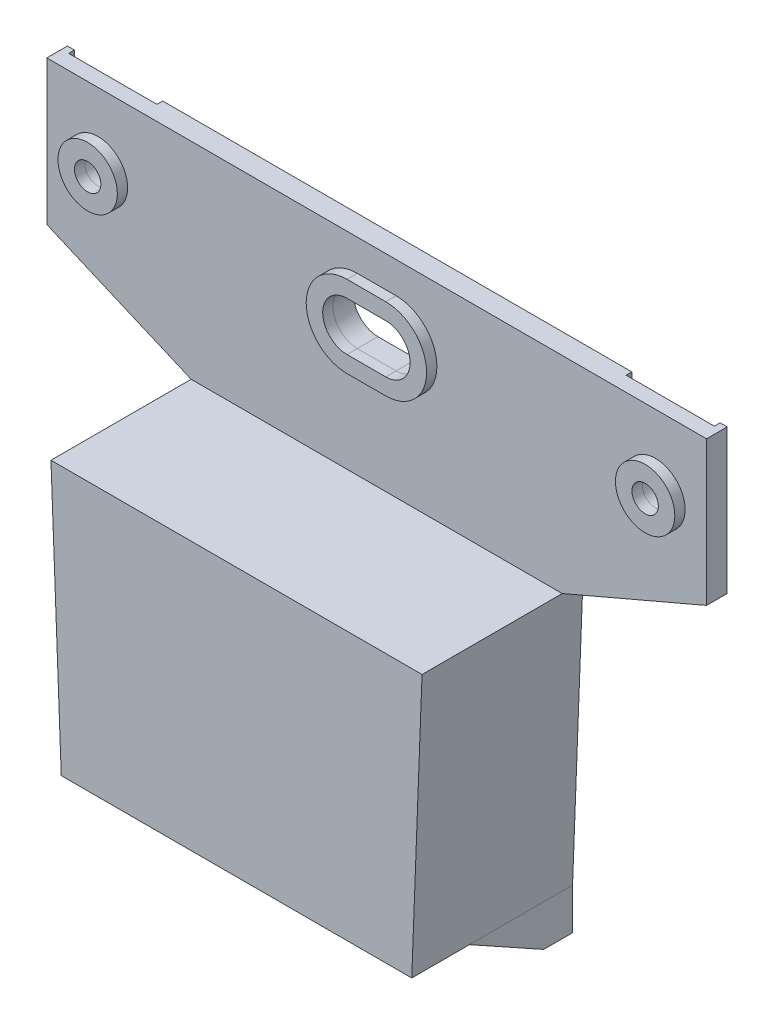
SolidWorks part; units mm, degrees
note: The reader was unsure of these and kept them because the rebuilt part matched: shared geometry of "Sketch17<2>".
ref_plane "Front Plane" through (0, 0, 0) normal (0, 0, 1) x (1, 0, 0)
ref_plane "Top Plane" through (0, 0, 0) normal (0, 1, 0) x (1, 0, 0)
ref_plane "Right Plane" through (0, 0, 0) normal (1, 0, 0) x (0, 0, -1)
sketch "Sketch1" plane through (0, 0, 0) normal (0, 0, 1) x (1, 0, 0)
  line L0 (-53.975, 0) -> (53.975, 0)
  line L1 (53.975, 0) -> (57.15, 82.55)
  line L2 (57.15, 82.55) -> (101.6, 101.6)
  line L3 (101.6, 101.6) -> (101.6, 146.05)
  line L4 (101.6, 146.05) -> (-101.6, 146.05)
  line L5 (-101.6, 146.05) -> (-101.6, 101.6)
  line L6 (-101.6, 101.6) -> (-57.15, 82.55)
  line L7 (-57.15, 82.55) -> (-53.975, 0)
  point P4 (0, 0)
  point P7 (0, 0)
  point P16 (0, 146.05)
  dimension "D1" = 44.45
  dimension "D2" = 44.45
  dimension "D3" = 146.05
  dimension "D4" = 107.95
  dimension "D5" = 203.2
  dimension "D6" = 114.3
  dimension "D7" = 19.05
base flange "Main Body" sketch "Sketch1" thickness 6.35 reverse thickness direction no parameters "D1"=1
sketch "Sketch6" plane through (0, 0, 0) normal (0, 0, 1) x (1, 0, 0)
  line L0 (53.975, 0) -> (-53.975, 0)
  line L1 (-53.975, 0) -> (-57.15, 82.55)
  line L2 (-57.15, 82.55) -> (57.15, 82.55)
  line L3 (57.15, 82.55) -> (53.975, 0)
  line L9 (-53.975, 0) -> (53.975, 0) construction
  point P10 (0, 0)
  point P11 (0, 82.55)
  dimension "D1" = 107.95
extrude "Pocket-Outer Surface" add sketch "Sketch6" along normal blind 43.18
sketch "Sketch7" plane through (0, 0, -6.35) normal (0, 0, -1) x (-1, 0, 0)
  line L0 (-50.5511, 76.2) -> (-47.8645, 6.35)
  line L1 (-47.8645, 6.35) -> (47.8645, 6.35)
  line L2 (47.8645, 6.35) -> (50.5511, 76.2)
  line L3 (50.5511, 76.2) -> (-50.5511, 76.2)
  line L5 (53.975, 0) -> (-53.975, 0) construction
  line L6 (57.15, 82.55) -> (53.975, 0) construction
  line L7 (-53.975, 0) -> (-57.15, 82.55) construction
  point P2 (0, 6.35)
  point P5 (0, 76.2)
  dimension "D1" = 6.35
  dimension "D2" = 6.35
  dimension "D3" = 69.85
extrude "Pocket-Inside" cut sketch "Sketch7" against normal blind 44.45 normal cut yes
sketch "Sketch8" plane through (0, 0, 0) normal (0, -1, 0) x (1, 0, 0)
  line L0 (-53.975, 25.4) -> (-53.975, -6.35)
  line L1 (-53.975, -6.35) -> (-53.975, 43.18) construction
  line L2 (-53.975, -6.35) -> (-41.275, -6.35)
  line L3 (-53.975, -6.35) -> (53.975, -6.35) construction
  line L4 (-41.275, -6.35) -> (-41.275, 25.4)
  line L5 (-41.275, 25.4) -> (-53.975, 25.4)
  dimension "D1" = 12.7
  dimension "D2" = 31.75
extrude "Bottom Screw Mount" add sketch "Sketch8" along normal blind 12.7
sketch "Sketch9" plane through (-53.975, 0, 0) normal (-1, 0, 0) x (0, 0, 1)
  line L0 (2.54, -12.7) -> (25.4, -12.7)
  line L1 (25.4, -12.7) -> (25.4, 0)
  line L2 (25.4, 0) -> (2.54, -12.7)
  dimension "D1" = 22.86
extrude "Bottom Screw Mount Extrusion" cut sketch "Sketch9" against normal through all normal cut yes
mirror "Left Bottom Screw Mount" about plane through (0, 0, 0) normal (1, 0, 0) of "Bottom Screw Mount Extrusion", "Bottom Screw Mount"
sketch "Sketch17" plane through (0, 0, 0) normal (0, 0, 1) x (1, 0, 0)
  line L0 (-5.969, 131.318) -> (5.969, 131.318)
  line L1 (5.969, 116.332) -> (-5.969, 116.332)
  line L2 (101.6, 146.05) -> (-101.6, 146.05) construction
  arc A0 (5.969, 131.318) -> (5.969, 116.332) centre (5.969, 123.825) cw
  arc A1 (-5.969, 116.332) -> (-5.969, 131.318) centre (-5.969, 123.825) cw
  circle A2 centre (85.852, 123.825) radius 4.064
  circle A3 centre (-85.852, 123.825) radius 4.064
  point P5 (1.524, 123.825)
  point P7 (-1.524, 123.825)
  point P8 (0, 131.318)
  point P9 (0, 116.332)
  point P12 (0, 146.05)
  point P15 (-13.462, 123.825)
  point P16 (13.462, 123.825)
  dimension "D4" = 72.39
  dimension "D1" = 26.924
  dimension "D2" = 14.986
  dimension "D3" = 14.732
  dimension "D5" = 72.39
extrude "Light Sockets" cut sketch "Sketch17" against normal blind 6.35 and the other way through all normal cut yes
sketch "Sketch18" plane through (0, 0, 0) normal (0, 0, 1) x (1, 0, 0)
  line L10 (5.969, 136.398) -> (-5.969, 136.398)
  line L11 (5.969, 136.398) -> (-5.969, 136.398)
  line L13 (-5.969, 111.252) -> (5.969, 111.252)
  line L14 (-5.969, 111.252) -> (5.969, 111.252)
  arc A4 (5.969, 111.252) -> (5.969, 136.398) centre (5.969, 123.825) ccw
  arc A5 (-5.969, 136.398) -> (-5.969, 111.252) centre (-5.969, 123.825) ccw
  arc A6 (5.969, 111.252) -> (5.969, 136.398) centre (5.969, 123.825) ccw
  arc A7 (-5.969, 136.398) -> (-5.969, 111.252) centre (-5.969, 123.825) ccw
  circle A12 centre (-85.852, 123.825) radius 9.144
  circle A13 centre (-85.852, 123.825) radius 9.144
  circle A15 centre (85.852, 123.825) radius 9.144
  circle A16 centre (85.852, 123.825) radius 9.144
  dimension "D1" = 5.08
  dimension "D2" = 5.08
  dimension "D3" = 5.08
  dimension "D4" = 5.08
extrude "Light Lip Liners" add sketch "Sketch18" along normal blind 3.175
extrude "Light Lip Sockets" cut sketch "Sketch17<2>" along normal up to next normal cut yes
sketch "Sketch17<2>" plane through (0, 0, 0) normal (0, 0, 1) x (1, 0, 0) same geometry as "Sketch17"
sketch "Sketch19" plane through (0, 0, -6.35) normal (0, 0, -1) x (-1, 0, 0)
  line L0 (72.263, 146.05) -> (72.263, 123.825)
  line L1 (-101.6, 146.05) -> (101.6, 146.05) construction
  line L2 (99.441, 123.825) -> (99.441, 146.05)
  line L3 (99.441, 146.05) -> (72.263, 146.05)
  arc A0 (72.263, 123.825) -> (99.441, 123.825) centre (85.852, 123.825) ccw
  circle A1 centre (85.852, 123.825) radius 4.064 construction
  dimension "D1" = 27.178
extrude "Tab Slots" cut sketch "Sketch19" against normal blind 1.778 normal cut yes
mirror "Mirror3" about plane through (0, 0, 0) normal (1, 0, 0) of "Tab Slots"
hole_wizard "1/4 (0.25) Diameter Hole1" positions "Sketch20" profile "Sketch21" hole size "1/4" standard "ANSI Inch" end condition through all
sketch "Sketch20" plane through (0, 0, -6.35) normal (0, 0, -1) x (-1, 0, 0)
  line L0 (53.975, 0) -> (-53.975, 0) construction
  line L1 (-53.975, -12.7) -> (-41.275, -12.7) construction
  line L2 (-53.975, -12.7) -> (-41.275, -12.7) construction
  line L3 (-47.625, -12.7) -> (-47.625, -6.35) construction
  line L5 (53.975, -12.7) -> (41.275, -12.7) construction
  line L6 (53.975, -12.7) -> (41.275, -12.7) construction
  line L7 (47.625, -12.7) -> (47.625, -6.35) construction
  point P0 (-47.625, -6.35)
  point P2 (47.625, -6.35)
  point P22 (0, 0)
  dimension "D1" = 6.35
  dimension "D2" = 6.35
sketch "Sketch21" plane through (47.625, -6.35, -6.35) normal (1, 0, 0) x (0, 1, 0)
  line L0 (0, 0) -> (0, 49.53)
  line L1 (0, 49.53) -> (3.175, 49.53)
  line L2 (3.175, 49.53) -> (3.175, 0)
  line L5 (3.175, 0) -> (0, 0)
  line L11 (0, -6.35) -> (0, 107.95) construction
  dimension "Thru Hole Dia." = 6.35
  dimension "Thru Hole Depth" = 49.53
sketch "Bend-Lines1" [suppressed] plane through (0, 0, 0) normal (0, 1, 0) x (1, 0, 0)
sketch "Bounding-Box1" [suppressed] plane through (0, 0, 0) normal (0, 1, 0) x (1, 0, 0)
sheet metal parameters "Sheet-Metal1" thickness 6.35 parameters "D1"=1
flat pattern "Flat-Pattern1" [suppressed]
sketch "Bend-Lines2" plane through (0, 0, 0) normal (0, 1, 0) x (1, 0, 0)
sketch3d "Bounding-Box2" [suppressed]
  line L0 (101.6, 0, 0) -> (-101.6, 0, 0) construction
  line L1 (101.6, 146.05, 0) -> (-101.6, 146.05, 0) construction
  line L2 (101.6, 0, 0) -> (101.6, 146.05, 0) construction
  line L3 (-101.6, 0, 0) -> (-101.6, 146.05, 0) construction
sheet metal parameters "Sheet-Metal2" thickness 6.35 parameters "D1"=1
flat pattern "Flat-Pattern1"
sketch "Bend-Lines2" plane through (0, 0, 0) normal (0, 1, 0) x (1, 0, 0)
sketch3d "Bounding-Box2" [suppressed]
  line L0 (-101.6, 75.6023, 0) -> (101.6, 75.6023, 0) construction
  line L1 (-101.6, 146.05, 0) -> (101.6, 146.05, 0) construction
  line L2 (-101.6, 75.6023, 0) -> (-101.6, 146.05, 0) construction
  line L3 (101.6, 75.6023, 0) -> (101.6, 146.05, 0) construction
sheet metal parameters "Sheet-Metal3" thickness 6.35 parameters "D1"=1
flat pattern "Flat-Pattern1"
sketch "Bend-Lines2" plane through (0, 0, 0) normal (0, 1, 0) x (1, 0, 0)
sketch3d "Bounding-Box2" [suppressed]
  line L0 (-101.6, 81.9986, 0) -> (101.6, 81.9986, 0) construction
  line L1 (-101.6, 146.05, 0) -> (101.6, 146.05, 0) construction
  line L2 (-101.6, 81.9986, 0) -> (-101.6, 146.05, 0) construction
  line L3 (101.6, 81.9986, 0) -> (101.6, 146.05, 0) construction
sheet metal parameters "Sheet-Metal4" thickness 6.35 parameters "D1"=1
flat pattern "Flat-Pattern1"
sketch "Bend-Lines2" plane through (0, 0, 0) normal (0, 1, 0) x (1, 0, 0)
sketch3d "Bounding-Box2" [suppressed]
  line L0 (-101.6, 81.9986, 0) -> (101.6, 81.9986, 0) construction
  line L1 (-101.6, 146.05, 0) -> (101.6, 146.05, 0) construction
  line L2 (-101.6, 81.9986, 0) -> (-101.6, 146.05, 0) construction
  line L3 (101.6, 81.9986, 0) -> (101.6, 146.05, 0) construction
sheet metal parameters "Sheet-Metal5" thickness 6.35 parameters "D1"=1
flat pattern "Flat-Pattern1" [suppressed]
sketch "Bend-Lines2" plane through (0, 0, 0) normal (0, 1, 0) x (1, 0, 0)
sketch3d "Bounding-Box2" [suppressed]
  line L0 (-101.6, 81.9986, 0) -> (101.6, 81.9986, 0) construction
  line L1 (-101.6, 146.05, 0) -> (101.6, 146.05, 0) construction
  line L2 (-101.6, 81.9986, 0) -> (-101.6, 146.05, 0) construction
  line L3 (101.6, 81.9986, 0) -> (101.6, 146.05, 0) construction
sketch "Sketch10-1" [suppressed] plane through (0, 0, -6.35) normal (0, 0, -1) x (-1, 0, 0)
  circle A0 centre (42.545, -5.08) radius 2.286
sheet metal parameters "Sheet-Metal8" thickness 6.35 parameters "D1"=1
flat pattern "Flat-Pattern1"
sketch "Bend-Lines2" plane through (0, 0, 0) normal (0, 1, 0) x (1, 0, 0)
sketch3d "Bounding-Box2" [suppressed]
  line L0 (-101.6, 81.9986, 0) -> (101.6, 81.9986, 0) construction
  line L1 (-101.6, 146.05, 0) -> (101.6, 146.05, 0) construction
  line L2 (-101.6, 81.9986, 0) -> (-101.6, 146.05, 0) construction
  line L3 (101.6, 81.9986, 0) -> (101.6, 146.05, 0) construction
sheet metal parameters "Sheet-Metal9" thickness 6.35 parameters "D1"=1
flat pattern "Flat-Pattern1"
sketch "Bend-Lines2" plane through (0, 0, 0) normal (0, 1, 0) x (1, 0, 0)
sketch3d "Bounding-Box2" [suppressed]
  line L0 (-101.6, 81.9986, 0) -> (101.6, 81.9986, 0) construction
  line L1 (-101.6, 146.05, 0) -> (101.6, 146.05, 0) construction
  line L2 (-101.6, 81.9986, 0) -> (-101.6, 146.05, 0) construction
  line L3 (101.6, 81.9986, 0) -> (101.6, 146.05, 0) construction
sheet metal parameters "Sheet-Metal10" thickness 6.35 parameters "D1"=1
flat pattern "Flat-Pattern1"
sketch "Bend-Lines2" plane through (0, 0, 0) normal (0, 1, 0) x (1, 0, 0)
sketch3d "Bounding-Box2" [suppressed]
  line L0 (-101.6, 81.9986, 0) -> (101.6, 81.9986, 0) construction
  line L1 (-101.6, 146.05, 0) -> (101.6, 146.05, 0) construction
  line L2 (-101.6, 81.9986, 0) -> (-101.6, 146.05, 0) construction
  line L3 (101.6, 81.9986, 0) -> (101.6, 146.05, 0) construction
sheet metal parameters "Sheet-Metal11" thickness 6.35 parameters "D1"=1
flat pattern "Flat-Pattern1"
sketch "Bend-Lines2" plane through (0, 0, 0) normal (0, 1, 0) x (1, 0, 0)
sketch3d "Bounding-Box2" [suppressed]
  line L0 (-101.6, 81.9986, 0) -> (101.6, 81.9986, 0) construction
  line L1 (-101.6, 146.05, 0) -> (101.6, 146.05, 0) construction
  line L2 (-101.6, 81.9986, 0) -> (-101.6, 146.05, 0) construction
  line L3 (101.6, 81.9986, 0) -> (101.6, 146.05, 0) construction
sheet metal parameters "Sheet-Metal12" thickness 6.35 parameters "D1"=1
flat pattern "Flat-Pattern1"
sketch "Bend-Lines2" plane through (0, 0, 0) normal (0, 1, 0) x (1, 0, 0)
sketch3d "Bounding-Box2" [suppressed]
  line L0 (-101.6, 81.9986, 0) -> (101.6, 81.9986, 0) construction
  line L1 (-101.6, 146.05, 0) -> (101.6, 146.05, 0) construction
  line L2 (-101.6, 81.9986, 0) -> (-101.6, 146.05, 0) construction
  line L3 (101.6, 81.9986, 0) -> (101.6, 146.05, 0) construction
sheet metal parameters "Sheet-Metal13" thickness 6.35 parameters "D1"=1
flat pattern "Flat-Pattern1"
sketch "Bend-Lines2" plane through (0, 0, 0) normal (0, 1, 0) x (1, 0, 0)
sketch3d "Bounding-Box2" [suppressed]
  line L0 (-101.6, 82.55, 0) -> (101.6, 82.55, 0) construction
  line L1 (-101.6, 146.05, 0) -> (101.6, 146.05, 0) construction
  line L2 (-101.6, 82.55, 0) -> (-101.6, 146.05, 0) construction
  line L3 (101.6, 82.55, 0) -> (101.6, 146.05, 0) construction
sheet metal parameters "Sheet-Metal14" thickness 6.35 parameters "D1"=1
flat pattern "Flat-Pattern1"
sketch "Bend-Lines2" plane through (0, 0, 0) normal (0, 1, 0) x (1, 0, 0)
sketch3d "Bounding-Box2" [suppressed]
  line L0 (-101.6, 82.55, 0) -> (101.6, 82.55, 0) construction
  line L1 (-101.6, 146.05, 0) -> (101.6, 146.05, 0) construction
  line L2 (-101.6, 82.55, 0) -> (-101.6, 146.05, 0) construction
  line L3 (101.6, 82.55, 0) -> (101.6, 146.05, 0) construction
